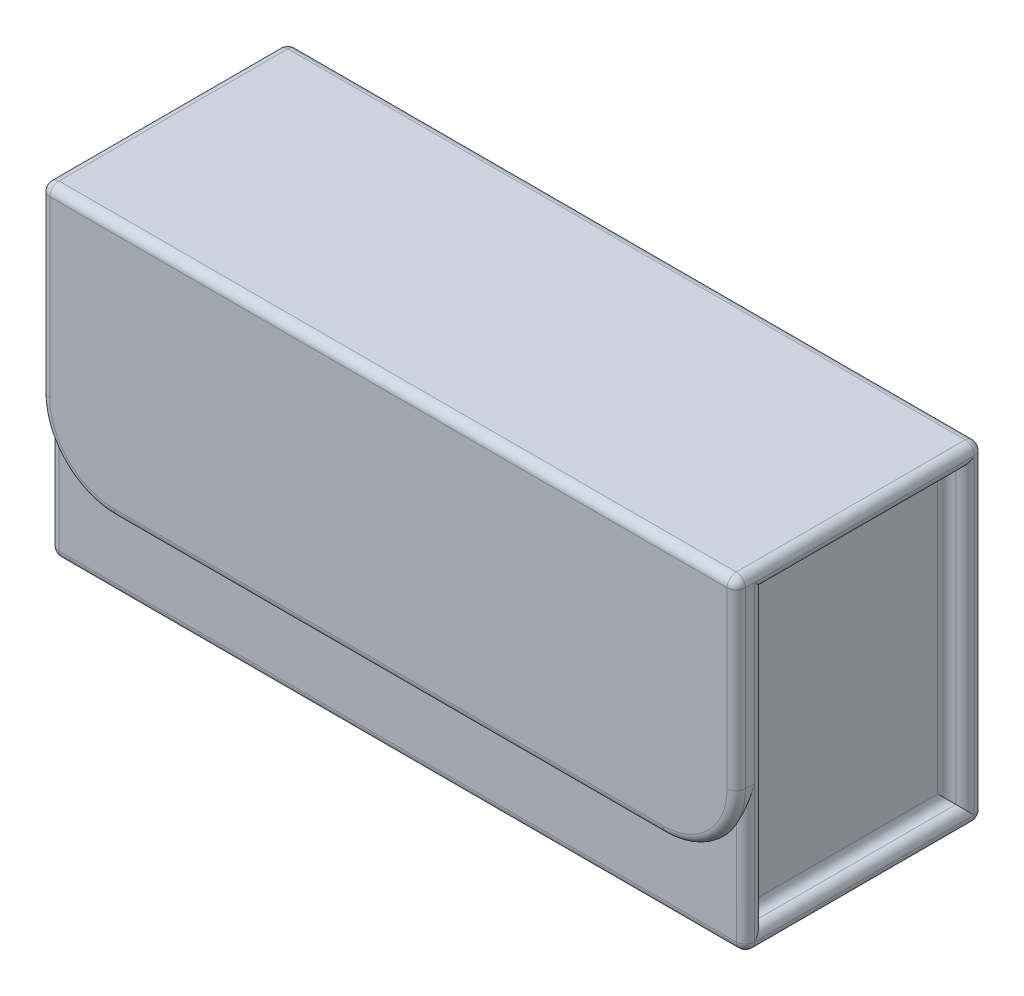
SolidWorks part; units mm, degrees
ref_plane "正面" through (0, 0, 0) normal (0, 0, 1) x (1, 0, 0)
ref_plane "平面" through (0, 0, 0) normal (0, 1, 0) x (1, 0, 0)
ref_plane "右側面" through (0, 0, 0) normal (1, 0, 0) x (0, 0, -1)
sketch "ｽｹｯﾁ1" plane through (0, 0, 0) normal (0, 1, 0) x (1, 0, 0)
  line L1 (-95, -32.5) -> (95, -32.5)
  line L2 (-95, -32.5) -> (-95, 32.5)
  line L3 (-95, 32.5) -> (95, 32.5)
  line L4 (95, -32.5) -> (95, 32.5)
  line L5 (-95, -32.5) -> (95, 32.5) construction
  line L6 (-95, 32.5) -> (95, -32.5) construction
  point P0 (0, 0)
  dimension "D1" = 65
  dimension "D2" = 190
extrude "ﾎﾞｽ - 押し出し1" add sketch "ｽｹｯﾁ1" along normal mid plane 90
fillet "ﾌｨﾚｯﾄ1" [suppressed] radius 5
sketch "ｽｹｯﾁ3" plane through (95, 0, 0) normal (1, 0, 0) x (0, 0, -1)
  line L0 (-27.5, -40) -> (27.5, -40)
  line L1 (27.5, -40) -> (27.5, 40)
  line L2 (27.5, 40) -> (-27.5, 40)
  line L3 (-27.5, 40) -> (-27.5, -40)
  line L4 (-32.5, -45) -> (32.5, -45)
  line L5 (-32.5, -45) -> (32.5, -45) construction
  line L6 (32.5, -45) -> (32.5, 45)
  line L7 (32.5, -45) -> (32.5, 45) construction
  line L12 (32.5, 45) -> (-32.5, 45)
  line L13 (32.5, 45) -> (-32.5, 45) construction
  line L14 (-32.5, 45) -> (-32.5, -45)
  line L15 (-32.5, 45) -> (-32.5, -45) construction
  dimension "D1" = 0
  dimension "D2" = 5
extrude "ｶｯﾄ - 押し出し1" cut sketch "ｽｹｯﾁ3" against normal blind 5
mirror "ﾐﾗｰ1" about plane through (0, 0, 0) normal (1, 0, 0) of "ｶｯﾄ - 押し出し1"
sketch "ｽｹｯﾁ4" plane through (0, 0, 32.5) normal (0, 0, 1) x (1, 0, 0)
  line L0 (95, 45) -> (95, -45) construction
  line L1 (-95, 45) -> (95, 45)
  line L2 (-95, 45) -> (-95, -5)
  line L3 (-75, -25) -> (75, -25)
  line L4 (95, 45) -> (95, -5)
  line L5 (-95, -45) -> (95, -45) construction
  arc A0 (75, -25) -> (95, -5) centre (75, -5) ccw
  arc A1 (-95, -5) -> (-75, -25) centre (-75, -5) ccw
  point P11 (95, -25)
  dimension "D2" = 20
  dimension "D1" = 20
extrude "ﾎﾞｽ - 押し出し2" add sketch "ｽｹｯﾁ4" along normal blind 2.5
fillet "ﾌｨﾚｯﾄ2" radius 2.5 26 edges at (0, -45, -32.5) (-95, -45, 0) (0, -45, 32.5) (95, -45, 0) (-90, -40, 0) (-90, 0, -27.5) (-90, 40, 0) (-90, 0, 27.5) (90, 40, 0) (90, 0, -27.5) (90, -40, 0) (90, 0, 27.5) (95, -25, 32.5) (95, 0, -32.5) (95, 45, 1.25) (95, 0, 27.5) (95, -40, 0) (95, 0, -27.5) (95, 40, 0) (-95, -25, 32.5) (-95, 0, -32.5) (-95, 45, 1.25) (-95, 0, -27.5) (-95, -40, 0) (-95, 0, 27.5) (-95, 40, 0)
fillet "ﾌｨﾚｯﾄ3" radius 2.5 8 edges at (94.2678, 44.2678, 35) (95, 18.75, 35) (89.1421, -19.1421, 35) (0, -25, 35) (-89.1421, -19.1421, 35) (-95, 18.75, 35) (-94.2678, 44.2678, 35) (0, 45, 35)
fillet "ﾌｨﾚｯﾄ4" radius 2.5 3 edges at (94.2678, 44.2678, -31.7678) (-94.2678, 44.2678, -31.7678) (0, 45, -32.5)
